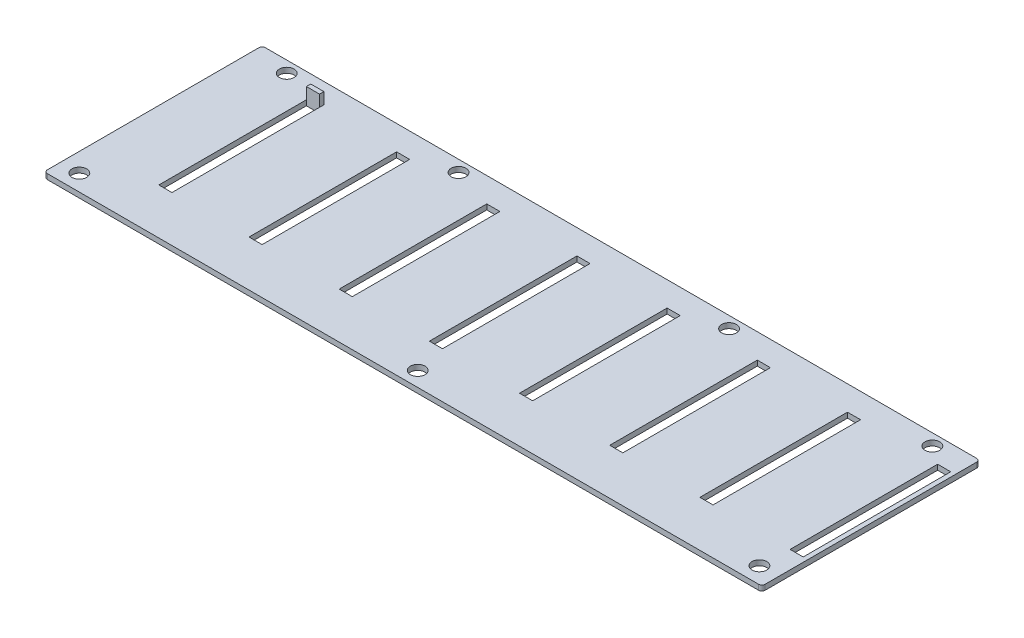
SolidWorks part; units mm, degrees
ref_plane "Front Plane" through (0, 0, 0) normal (0, 0, 1) x (1, 0, 0)
ref_plane "Top Plane" through (0, 0, 0) normal (0, 1, 0) x (1, 0, 0)
ref_plane "Right Plane" through (0, 0, 0) normal (1, 0, 0) x (0, 0, -1)
sketch "Sketch1" plane through (0, 0, 0) normal (0, 1, 0) x (1, 0, 0)
  line L0 (-343.6338, -10.1642) -> (262.3662, -10.1642) construction
  line L1 (0, 0) -> (218.9, 0)
  line L2 (0, 0) -> (0, 66.5)
  line L3 (0, 66.5) -> (218.9, 66.5)
  line L4 (218.9, 0) -> (218.9, 66.5)
  line L6 (21, 59) -> (25, 59)
  line L7 (21, 59) -> (21, 14)
  line L8 (21, 14) -> (25, 14)
  line L9 (25, 59) -> (25, 14)
  line L10 (48.5, 59) -> (52.5, 59)
  line L11 (48.5, 59) -> (48.5, 14)
  line L12 (48.5, 14) -> (52.5, 14)
  line L13 (52.5, 59) -> (52.5, 14)
  line L14 (76, 59) -> (80, 59)
  line L15 (76, 59) -> (76, 14)
  line L16 (76, 14) -> (80, 14)
  line L17 (80, 59) -> (80, 14)
  line L18 (103.5, 59) -> (107.5, 59)
  line L19 (103.5, 59) -> (103.5, 14)
  line L20 (103.5, 14) -> (107.5, 14)
  line L21 (107.5, 59) -> (107.5, 14)
  line L22 (131, 59) -> (135, 59)
  line L23 (131, 59) -> (131, 14)
  line L24 (131, 14) -> (135, 14)
  line L25 (135, 59) -> (135, 14)
  line L26 (158.5, 59) -> (162.5, 59)
  line L27 (158.5, 59) -> (158.5, 14)
  line L28 (158.5, 14) -> (162.5, 14)
  line L29 (162.5, 59) -> (162.5, 14)
  line L30 (186, 59) -> (190, 59)
  line L31 (186, 59) -> (186, 14)
  line L32 (186, 14) -> (190, 14)
  line L33 (190, 59) -> (190, 14)
  line L34 (213.5, 59) -> (217.5, 59)
  line L35 (213.5, 59) -> (213.5, 14)
  line L36 (213.5, 14) -> (217.5, 14)
  line L37 (217.5, 59) -> (217.5, 14)
  circle A0 centre (11, 63) radius 2.25
  circle A1 centre (63.4, 63) radius 2.25
  circle A2 centre (145.9, 63) radius 2.25
  circle A3 centre (207.9, 63) radius 2.25
  circle A4 centre (5.75, 5) radius 2.25
  circle A5 centre (109.45, 4.5) radius 2.25
  circle A6 centre (213.15, 5) radius 2.25
  dimension "D3" = 3.5
  dimension "D5" = 3.5
  dimension "D7" = 3.5
  dimension "D9" = 3.5
  dimension "D11" = 5
  dimension "D13" = 4.5
  dimension "D15" = 5
  dimension "D1" = 218.9
  dimension "D2" = 66.5
  dimension "D4" = 11
  dimension "D6" = 52.4
  dimension "D8" = 82.5
  dimension "D10" = 62
  dimension "D12" = 5.75
  dimension "D14" = 103.7
  dimension "D16" = 103.7
  dimension "D17" = 4
  dimension "D18" = 45
  dimension "D19" = 21
  dimension "D20" = 7.5
  dimension "D21" = 27.5
  dimension "D22" = 4
  dimension "D23" = 45
  dimension "D24" = 7.5
  dimension "D25" = 4
  dimension "D26" = 45
  dimension "D27" = 7.5
  dimension "D28" = 27.5
  dimension "D29" = 27.5
  dimension "D30" = 4
  dimension "D31" = 45
  dimension "D32" = 7.5
  dimension "D33" = 27.5
  dimension "D34" = 45
  dimension "D35" = 4
  dimension "D36" = 7.5
  dimension "D37" = 27.5
  dimension "D38" = 4
  dimension "D39" = 45
  dimension "D40" = 7.5
  dimension "D41" = 27.5
  dimension "D42" = 4
  dimension "D43" = 45
  dimension "D44" = 7.5
  dimension "D45" = 45
  dimension "D46" = 7.5
  dimension "D47" = 27.5
  dimension "D48" = 4
extrude "Boss-Extrude1" add sketch "Sketch1" along normal blind 1.6
fillet "Fillet1" radius 1 4 edges at (218.9, 0.8, -66.5) (218.9, 0.8, 0) (0, 0.8, 0) (0, 0.8, -66.5)
ref_plane "Plane1" through (21, 1.6, -14) normal (0, 0, 1) x (1, 0, 0)
sketch "Sketch3" plane through (0, 0, 0) normal (0, 1, 0) x (1, 0, 0)
  line L1 (21, 59) -> (25, 59)
  line L2 (21, 59) -> (21, 60.3316)
  line L3 (21, 60.3316) -> (25, 60.3316)
  line L4 (25, 59) -> (25, 60.3316)
extrude "Boss-Extrude2" add sketch "Sketch3" along normal blind 5.1
